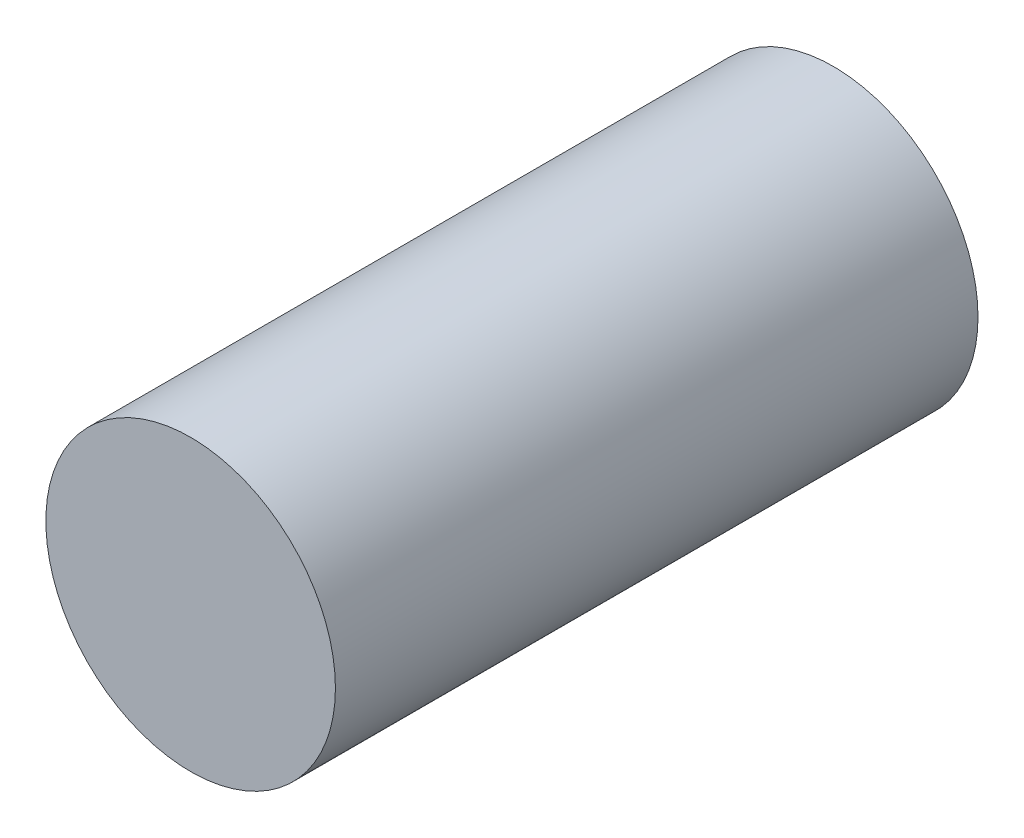
SolidWorks part; units mm, degrees
ref_plane "Front Plane" through (0, 0, 0) normal (0, 0, 1) x (1, 0, 0)
ref_plane "Top Plane" through (0, 0, 0) normal (0, 1, 0) x (1, 0, 0)
ref_plane "Right Plane" through (0, 0, 0) normal (1, 0, 0) x (0, 0, -1)
sketch "Planform" plane through (0, 0, 0) normal (0, 1, 0) x (1, 0, 0)
  line L0 (0, 0) -> (0, -7497.1177)
  line L1 (-17711.9405, -11444.2752) -> (-17711.9405, -14068.2664)
  line L2 (0, -1874.2794) -> (-17711.9405, -12100.273) construction
  line L3 (0, -1874.2794) -> (-6644.0672, -1874.2794) construction
  line L4 (0, 0) -> (-17711.9405, -11444.2752)
  line L5 (0, -7497.1177) -> (-17711.9405, -14068.2664)
  dimension "D1" = 7497.1177
  dimension "D2" = 2623.9912
  dimension "D3" = 1874.2794
  dimension "D4" = 655.9978
  dimension "D5" = 30
  dimension "D6" = 17711.9405
sketch "Sketch1" plane through (0, 0, 0) normal (0, 0, 1) x (1, 0, 0)
  circle A0 centre (0, 0) radius 1330.7871
  dimension "D1" = 2661.5742
extrude "Nacelle body" add sketch "Sketch1" along normal blind 5906.115
sketch "Black front" plane through (0, 0, 5906.115) normal (0, 0, 1) x (1, 0, 0)
  line L0 (59.2242, 1082.815) -> (229.8908, 1082.815) construction
sketch "Location" plane through (0, 0, 0) normal (0, 1, 0) x (1, 0, 0)
  line L0 (-1330.7871, -1066.8892) -> (1330.7871, -1066.8892)
  line L1 (1330.7871, 0) -> (-1330.7871, 0)
  line L2 (1330.7871, 0) -> (1330.7871, -5906.115)
  line L3 (1330.7871, -5906.115) -> (-1330.7871, -5906.115)
  line L4 (-1330.7871, 0) -> (-1330.7871, -5906.115)
  line L5 (-1330.7871, 0) -> (1330.7871, -5906.115)
  line L6 (1330.7871, 0) -> (-1330.7871, -5906.115)
  line L7 (1330.7871, -2953.0575) -> (-1330.7871, -2953.0575)
  point P9 (0, -1066.8892)
  point P11 (0, -2953.0575)
  dimension "D1" = 2661.5742
  dimension "D2" = 4839.2257
equation "\"Diameter\" = 7.938362438 * 1.1"
equation "\"Length\"= 19.37701766"
equation "\"D1@Sketch1\"=\"Diameter\""
equation "\"D1@Nacelle body\"=\"Length\""
equation "\"D2@Location\"=\"Diameter\"/1.1*2"
